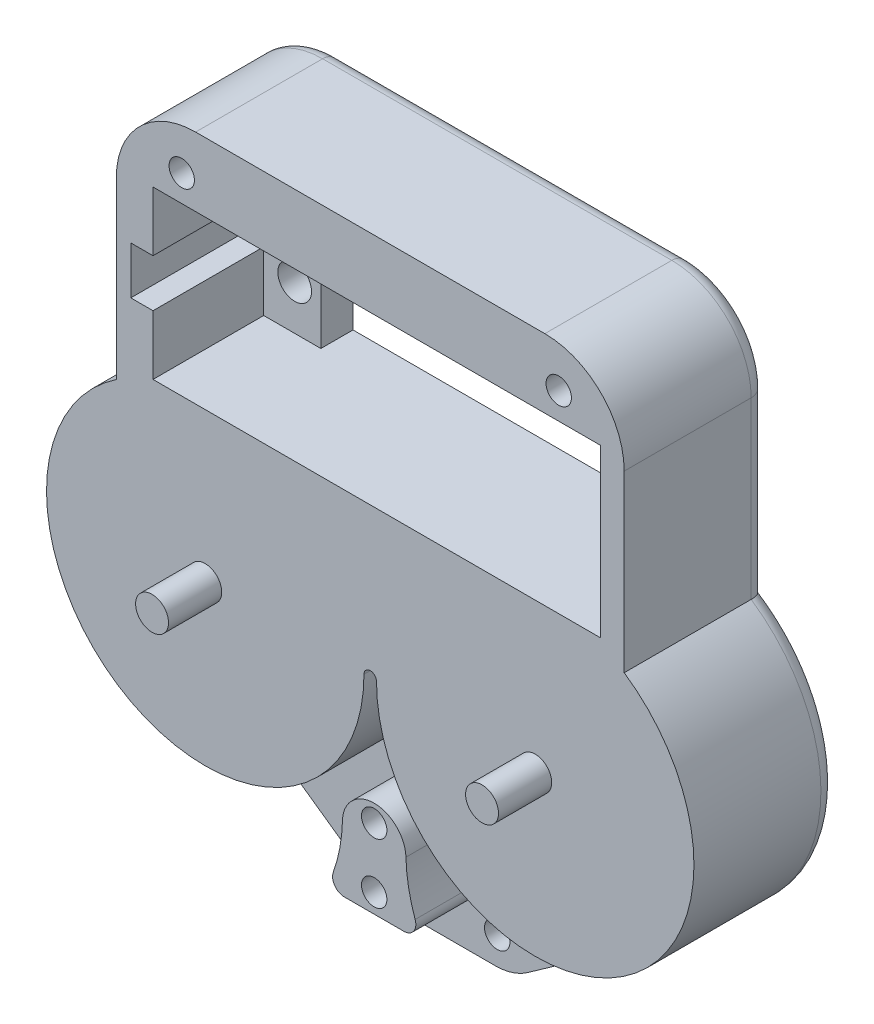
SolidWorks part; units mm, degrees
ref_plane "Alzado" through (0, 0, 0) normal (0, 0, 1) x (1, 0, 0)
ref_plane "Planta" through (0, 0, 0) normal (0, 1, 0) x (1, 0, 0)
ref_plane "Vista lateral" through (0, 0, 0) normal (1, 0, 0) x (0, 0, -1)
sketch "Croquis1" plane through (0, 0, 0) normal (0, 0, 1) x (1, 0, 0)
  line L0 (-9.1775, 40) -> (9.1775, 40)
  line L2 (32.3363, -22.7922) -> (8, -40)
  line L3 (8, -40) -> (-8, -40)
  line L4 (0, 40) -> (0, -40) construction
  line L5 (-32.3363, -22.7922) -> (-8, -40)
  line L7 (24.4498, 13.2001) -> (24.4498, 27.2001)
  line L8 (-24.4498, 13.2001) -> (-24.4498, 27.2001)
  arc A1 (24.4498, 13.2001) -> (32.3363, -22.7922) centre (20.7895, -6.4621) cw
  arc A3 (-24.4498, 13.2001) -> (-32.3363, -22.7922) centre (-20.7895, -6.4621) ccw
  arc A4 (24.4498, 27.2001) -> (9.1775, 40) centre (11.4498, 27.2001) ccw
  arc A5 (-24.4498, 27.2001) -> (-9.1775, 40) centre (-11.4498, 27.2001) cw
  point P7 (0, 0)
  dimension "D4" = 14
  dimension "D5" = 13
  dimension "D2" = 20
  dimension "D1" = 9.1775
  dimension "D3" = 80
  dimension "D6" = 8
extrude "Saliente-Extruir1" add sketch "Croquis1" along normal blind 20 contours A3 L5 L3 L2 A1 L7 A4 L0 A5 L8
sketch "Croquis2" plane through (0, 0, 20) normal (0, 0, 1) x (1, 0, 0)
  line L0 (-20.7895, -6.4621) -> (-0.0045, -6.4621) construction
  line L1 (20.7895, -6.4621) -> (0.0045, -6.4621) construction
  line L2 (0, -40) -> (0, 40) construction
  line L3 (8, -40) -> (-8, -40) construction
  line L4 (-9.1775, 40) -> (9.1775, 40) construction
  arc A0 (0, 2.143) -> (0, -15.0672) centre (-20.7895, -6.4621) ccw
  arc A1 (0, -15.0672) -> (18.9832, 15.9653) centre (20.7895, -6.4621) ccw
  circle A2 centre (-20.7895, -6.4621) radius 20.785 construction
  circle A3 centre (20.7895, -6.4621) radius 20.785 construction
  arc A6 (18.9832, 15.9653) -> (5.6059, 10.1424) centre (8, 22.9201) ccw
  circle A7 centre (8, 22.9201) radius 11.26 construction
  arc A8 (5.6059, 10.1424) -> (0, 2.143) centre (20.7895, -6.4621) ccw
  dimension "D1" = 45
  dimension "D2" = 41.57
  dimension "D3" = 26
  dimension "D4" = 22.52
  dimension "D5" = 8
extrude "Cortar-Extruir1" cut sketch "Croquis2" against normal blind 12 contours A0 A1 A6 A8
sketch "Croquis3" plane through (0, 0, 20) normal (0, 0, 1) x (1, 0, 0)
  line L3 (-23.9199, -28.7432) -> (-8, -40)
  line L4 (-8, -40) -> (8, -40)
  line L5 (8, -40) -> (23.9199, -28.7432)
  line L6 (-23.9199, -28.7432) -> (-8, -40)
  line L7 (-8, -40) -> (8, -40)
  line L8 (8, -40) -> (23.9199, -28.7432)
  arc A2 (0, -15.0672) -> (23.9199, -28.7432) centre (20.7895, -6.4621) ccw
  arc A3 (-23.9199, -28.7432) -> (0, -15.0672) centre (-20.7895, -6.4621) ccw
  arc A4 (0, -15.0672) -> (23.9199, -28.7432) centre (20.7895, -6.4621) ccw
  arc A5 (-23.9199, -28.7432) -> (0, -15.0672) centre (-20.7895, -6.4621) ccw
  dimension "D1" = 0
extrude "Cortar-Extruir2" cut sketch "Croquis3" against normal up to surface (12 mm away) up to face at (1.4203, -0.7032, 8)
sketch "Croquis4" plane through (0, 0, 8) normal (0, 0, 1) x (1, 0, 0)
  circle A0 centre (-20.7895, -6.4621) radius 2.1
  circle A1 centre (20.7895, -6.4621) radius 2.1
  circle A2 centre (8, 22.9201) radius 2.1
  dimension "D1" = 4.2
extrude "Saliente-Extruir2" add sketch "Croquis4" along normal blind 6.7
fillet "Redondeo2" radius 7 2 edges at (8, -40, 4) (-8, -40, 4)
sketch "Croquis5" plane through (0, 0, 8) normal (0, 0, 1) x (1, 0, 0)
  line L0 (0, -40) -> (0, 0) construction
  line L1 (5.7752, -40) -> (-5.7752, -40) construction
  circle A0 centre (6, -36.5) radius 3.5 construction
  circle A1 centre (6, -36.5) radius 1.6
  circle A2 centre (-6, -36.5) radius 1.6
  circle A3 centre (-6, -36.5) radius 3.5 construction
  dimension "D1" = 7
  dimension "D2" = 3.2
  dimension "D3" = 6
extrude "Cortar-Extruir3" cut sketch "Croquis5" against normal through all
sketch "Croquis6" plane through (0, 0, 8) normal (0, 0, 1) x (1, 0, 0)
  line L0 (-6, -32.5) -> (6, -32.5)
  line L2 (0, -40) -> (0, 40) construction
  line L3 (5.7752, -40) -> (-5.7752, -40) construction
  line L4 (0, -32.5) -> (0, -20) construction
  arc A1 (6, -32.5) -> (3.9987, -24.28) centre (23.9921, -23.7658) cw
  arc A2 (3.9987, -24.28) -> (-3.9987, -24.28) centre (0, -24.3828) ccw
  arc A3 (-6, -32.5) -> (-3.9987, -24.28) centre (-23.9921, -23.7658) ccw
  point P3 (0, -32.5)
  dimension "D2" = 20
  dimension "D1" = 7.5
  dimension "D3" = 8.22
  dimension "D4" = 12
  dimension "D6" = 4
extrude "Saliente-Extruir3" add sketch "Croquis6" along normal blind 9.5 contours A1 A2 A3 L0
fillet "Redondeo3" radius 1.5 2 edges at (6, -32.5, 12.75) (-6, -32.5, 12.75)
sketch "Croquis7" plane through (0, 0, 17.5) normal (0, 0, 1) x (1, 0, 0)
  line L0 (0, -32.5) -> (0, -20.3828) construction
  line L1 (-3.7457, -32.5) -> (3.7457, -32.5) construction
  line L2 (0, -20.3828) -> (0, -40) construction
  arc A0 (3.9987, -24.28) -> (-3.9987, -24.28) centre (0, -24.3828) ccw construction
  circle A1 centre (0, -22.5614) radius 1.6
  circle A2 centre (0, -30.1014) radius 1.6
  point P11 (0, -26.4414)
  dimension "D1" = 3.2
  dimension "D2" = 3.88
  dimension "D3" = 3.66
extrude "Cortar-Extruir4" cut sketch "Croquis7" against normal through all
sketch "Croquis8" plane through (0, 0, 20) normal (0, 0, 1) x (1, 0, 0)
  line L3 (24.4498, 15.7382) -> (24.4498, 27.2001)
  line L4 (9.1775, 40) -> (-9.1775, 40)
  line L5 (-24.4498, 27.2001) -> (-24.4498, 15.7382)
  line L6 (24.4498, 15.7382) -> (24.4498, 27.2001)
  line L7 (9.1775, 40) -> (-9.1775, 40)
  line L8 (-24.4498, 27.2001) -> (-24.4498, 15.7382)
  arc A11 (5.6059, 10.1424) -> (0, 2.143) centre (20.7895, -6.4621) ccw
  arc A13 (18.9832, 15.9653) -> (5.6059, 10.1424) centre (8, 22.9201) ccw
  arc A15 (24.4498, 15.7382) -> (18.9832, 15.9653) centre (20.7895, -6.4621) ccw
  arc A17 (24.4498, 27.2001) -> (9.1775, 40) centre (11.4498, 27.2001) ccw
  arc A18 (-9.1775, 40) -> (-24.4498, 27.2001) centre (-11.4498, 27.2001) ccw
  arc A20 (0, 2.143) -> (-24.4498, 15.7382) centre (-20.7895, -6.4621) ccw
  arc A22 (5.6059, 10.1424) -> (0, 2.143) centre (20.7895, -6.4621) ccw
  arc A24 (18.9832, 15.9653) -> (5.6059, 10.1424) centre (8, 22.9201) ccw
  arc A26 (24.4498, 15.7382) -> (18.9832, 15.9653) centre (20.7895, -6.4621) ccw
  arc A28 (24.4498, 27.2001) -> (9.1775, 40) centre (11.4498, 27.2001) ccw
  arc A29 (-9.1775, 40) -> (-24.4498, 27.2001) centre (-11.4498, 27.2001) ccw
  arc A31 (0, 2.143) -> (-24.4498, 15.7382) centre (-20.7895, -6.4621) ccw
  dimension "D1" = 0
extrude "Cortar-Extruir5" cut sketch "Croquis8" against normal up to surface (12 mm away) up to face at (0, -28.5797, 8)
sketch "Croquis9" plane through (0, 0, 14.7) normal (0, 0, 1) x (1, 0, 0)
  circle A0 centre (20.7895, -6.4621) radius 2.1 construction
  circle A1 centre (8, 22.9201) radius 2.1
  circle A2 centre (8, 22.9201) radius 2.1
  circle A3 centre (-20.7895, -6.4621) radius 2.1 construction
  circle A4 centre (20.7895, -6.4621) radius 2.1
  circle A5 centre (-20.7895, -6.4621) radius 2.1
  dimension "D1" = 0
extrude "Cortar-Extruir6" cut sketch "Croquis9" against normal up to surface (6.7 mm away) up to face at (0, -2.5404, 8)
sketch "Croquis10" plane through (0, 0, 8) normal (0, 0, 1) x (1, 0, 0)
  line L0 (24.4498, 13.2001) -> (24.4498, 27.2001) construction
  line L1 (-9.1775, 40) -> (9.1775, 40) construction
  line L2 (-24.4498, 13.2001) -> (-24.4498, 27.2001) construction
  line L3 (24.4498, 13.2001) -> (24.4498, 27.2001)
  line L4 (-9.1775, 40) -> (9.1775, 40)
  line L5 (-24.4498, 13.2001) -> (-24.4498, 27.2001)
  line L6 (24.4498, 13.2001) -> (24.4498, -26.1243) construction
  line L7 (-24.4498, 13.2001) -> (-24.4498, -26.1243) construction
  line L8 (-24.4498, -6.4621) -> (24.4498, -6.4621) construction
  line L9 (20.7895, -6.4621) -> (0.0045, -6.4621) construction
  line L10 (-20.7895, -6.4621) -> (-0.0045, -6.4621) construction
  arc A5 (24.4498, 27.2001) -> (9.1775, 40) centre (11.4498, 27.2001) ccw construction
  arc A6 (-9.1775, 40) -> (-24.4498, 27.2001) centre (-11.4498, 27.2001) ccw construction
  arc A7 (24.4498, 27.2001) -> (9.1775, 40) centre (11.4498, 27.2001) ccw
  arc A8 (-9.1775, 40) -> (-24.4498, 27.2001) centre (-11.4498, 27.2001) ccw
  arc A9 (32.3363, -22.7922) -> (24.4498, 13.2001) centre (20.7895, -6.4621) ccw construction
  arc A10 (-24.4498, 13.2001) -> (-32.3363, -22.7922) centre (-20.7895, -6.4621) ccw construction
  arc A11 (24.4498, -26.1243) -> (24.4498, 13.2001) centre (20.7895, -6.4621) ccw
  arc A12 (-24.4498, 13.2001) -> (-24.4498, -26.1243) centre (-20.7895, -6.4621) ccw
  arc A13 (-24.4498, 13.2001) -> (-0.7895, -6.4621) centre (-20.7895, -6.4621) ccw
  arc A14 (0.7895, -6.4621) -> (24.4498, 13.2001) centre (20.7895, -6.4621) ccw
  arc A15 (-0.7895, -6.4621) -> (0.7895, -6.4621) centre (0, -6.4621) cw
sketch "Croquis11" plane through (0, 0, 8) normal (0, 0, 1) x (1, 0, 0)
  line L0 (24.4498, 13.2001) -> (24.4498, 27.2001) construction
  line L1 (-9.1775, 40) -> (9.1775, 40) construction
  line L2 (-24.4498, 13.2001) -> (-24.4498, 27.2001) construction
  line L3 (24.4498, 13.2001) -> (24.4498, 27.2001)
  line L4 (-9.1775, 40) -> (9.1775, 40)
  line L5 (-24.4498, 13.2001) -> (-24.4498, 27.2001)
  arc A0 (24.4498, 27.2001) -> (9.1775, 40) centre (11.4498, 27.2001) ccw construction
  arc A1 (-9.1775, 40) -> (-24.4498, 27.2001) centre (-11.4498, 27.2001) ccw construction
  arc A2 (24.4498, 27.2001) -> (9.1775, 40) centre (11.4498, 27.2001) ccw
  arc A3 (-9.1775, 40) -> (-24.4498, 27.2001) centre (-11.4498, 27.2001) ccw
  arc A4 (32.3363, -22.7922) -> (24.4498, 13.2001) centre (20.7895, -6.4621) ccw construction
  arc A5 (-24.4498, 13.2001) -> (-32.3363, -22.7922) centre (-20.7895, -6.4621) ccw construction
  arc A6 (24.4498, -26.1243) -> (24.4498, 13.2001) centre (20.7895, -6.4621) ccw
  arc A7 (-24.4498, 13.2001) -> (-24.4498, -26.1243) centre (-20.7895, -6.4621) ccw
  arc A8 (-24.4498, -26.1243) -> (-0.7895, -6.4621) centre (-20.7895, -6.4621) ccw
  arc A9 (24.4498, -26.1243) -> (0.7895, -6.4621) centre (20.7895, -6.4621) cw
  arc A10 (-0.7895, -6.4621) -> (0.7895, -6.4621) centre (0, -6.4621) cw
extrude "Saliente-Extruir4" add sketch "Croquis11" along normal blind 10
sketch "Croquis12" plane through (0, 0, 18) normal (0, 0, 1) x (1, 0, 0)
  circle A0 centre (-20.7895, -6.4621) radius 2.075
  circle A1 centre (20.7895, -6.4621) radius 2.075
  dimension "D1" = 4.15
extrude "Saliente-Extruir5" add sketch "Croquis12" along normal blind 6.7
sketch "Croquis14" plane through (0, 0, 18) normal (0, 0, 1) x (1, 0, 0)
  line L1 (-32, 32.1007) -> (-32, 10.1007)
  line L2 (-24.4498, 27.2001) -> (-24.4498, 13.2001) construction
  line L3 (-24.4498, 27.2001) -> (-24.4498, 13.2001)
  line L4 (-22, 42.1007) -> (22, 42.1007)
  line L5 (32, 32.1007) -> (32, 10.1007)
  line L6 (24.4498, 13.2001) -> (24.4498, 27.2001) construction
  line L7 (9.1775, 40) -> (-9.1775, 40) construction
  line L8 (24.4498, 13.2001) -> (24.4498, 27.2001)
  line L9 (9.1775, 40) -> (-9.1775, 40)
  arc A0 (-24.4498, 13.2001) -> (-0.7895, -6.4621) centre (-20.7895, -6.4621) ccw construction
  arc A1 (-9.1775, 40) -> (-24.4498, 27.2001) centre (-11.4498, 27.2001) ccw construction
  arc A2 (-9.1775, 40) -> (-24.4498, 27.2001) centre (-11.4498, 27.2001) ccw
  arc A3 (-24.4498, 13.2001) -> (-32, 10.1007) centre (-20.7895, -6.4621) ccw
  arc A4 (0.7895, -6.4621) -> (24.4498, 13.2001) centre (20.7895, -6.4621) ccw construction
  arc A5 (24.4498, 27.2001) -> (9.1775, 40) centre (11.4498, 27.2001) ccw construction
  arc A6 (32, 10.1007) -> (24.4498, 13.2001) centre (20.7895, -6.4621) ccw
  arc A7 (24.4498, 27.2001) -> (9.1775, 40) centre (11.4498, 27.2001) ccw
  arc A8 (22, 42.1007) -> (32, 32.1007) centre (22, 32.1007) cw
  arc A9 (-22, 42.1007) -> (-32, 32.1007) centre (-22, 32.1007) ccw
  point P5 (0, 42.1007)
  point P23 (-32, 42.1007)
  dimension "D3" = 10
  dimension "D1" = 32
  dimension "D2" = 64
extrude "Saliente-Extruir6" add sketch "Croquis14" against normal up to surface (18 mm away) up to face at (1.6, -22.5614, 0)
fillet "Redondeo1" radius 2 12 edges at (-40.7884, -6.2576, 0) (-21.0764, -30.7538, 0) (0, -40, 0) (21.0764, -30.7538, 0) (40.7884, -6.2576, 0) (29.0711, 39.1717, 0) (0, 42.1007, 0) (-29.0711, 39.1717, 0) (-32, 21.1007, 0) (-7.8955, -39.6712, 0) (7.8955, -39.6712, 0) (32, 21.1007, 0)
sketch "Croquis13" plane through (0, 0, 18) normal (0, 0, 1) x (1, 0, 0)
  line L0 (0.83, 33.4201) -> (0.83, 12.4201) construction
  line L5 (-27.37, 33.4201) -> (29.03, 33.4201)
  line L6 (-27.37, 33.4201) -> (-27.37, 12.4201)
  line L7 (-27.37, 12.4201) -> (29.03, 12.4201)
  line L8 (29.03, 33.4201) -> (29.03, 12.4201)
  point P4 (29.03, 22.9201)
  dimension "D1" = 21.03
  dimension "D2" = 56.4
  dimension "D3" = 21
extrude "Cortar-Extruir7" cut sketch "Croquis13" against normal blind 13.95
sketch "Croquis15" plane through (0, 0, 4.05) normal (0, 0, 1) x (1, 0, 0)
  line L5 (29.03, 33.4201) -> (-27.37, 33.4201) construction
  line L6 (-20.17, 33.4201) -> (21.83, 33.4201)
  line L13 (-20.17, 33.4201) -> (-20.17, 12.4201)
  line L14 (-20.17, 12.4201) -> (21.83, 12.4201)
  line L15 (21.83, 33.4201) -> (21.83, 12.4201)
  line L16 (-27.37, 12.4201) -> (29.03, 12.4201) construction
  line L17 (0.83, 33.4201) -> (0.83, 12.4201) construction
  point P5 (0.83, 33.4201)
  dimension "D1" = 42
extrude "Cortar-Extruir8" cut sketch "Croquis15" against normal through all
sketch "Croquis16" [suppressed] plane through (0, 0, 4.05) normal (0, 0, 1) x (1, 0, 0)
  circle A0 centre (1.5743, 28.719) radius 2.125
  circle A1 centre (1.5743, 18.969) radius 2.125
  circle A2 centre (50.1743, 28.719) radius 2.125
  circle A3 centre (50.1743, 18.969) radius 2.125
sketch "Croquis18" plane through (0, 0, 0) normal (0, 0, -1) x (-1, 0, 0)
  circle A0 centre (0, -22.5614) radius 3.66
  circle A2 centre (6, -36.5) radius 3.66
  circle A3 centre (-6, -36.5) radius 3.66
  circle A4 centre (0, -30.1014) radius 3.66
  dimension "D1" = 7.32
extrude "Cortar-Extruir11" cut sketch "Croquis18" against normal blind 2.67
sketch "Croquis17" plane through (0, 0, 0) normal (0, 0, -1) x (-1, 0, 0)
  line L1 (-43.4093, 11.1522) -> (43.8711, 11.1522)
  line L2 (-43.4093, 11.1522) -> (-43.4093, -41.3776)
  line L3 (-43.4093, -41.3776) -> (43.8711, -41.3776)
  line L4 (43.8711, 11.1522) -> (43.8711, -41.3776)
sketch "Croquis19" plane through (0, 0, 0) normal (0, 0, -1) x (-1, 0, 0)
  line L6 (20.17, 25.9201) -> (30.17, 25.9201)
  line L7 (20.17, 25.9201) -> (20.17, 19.9201)
  line L8 (20.17, 19.9201) -> (30.17, 19.9201)
  line L9 (30.17, 25.9201) -> (30.17, 19.9201)
  line L10 (20.17, 33.4201) -> (20.17, 12.4201) construction
  point P4 (20.17, 22.9201)
  point P5 (20.17, 22.9201)
  dimension "D1" = 10
  dimension "D2" = 6
extrude "Cortar-Extruir12" cut sketch "Croquis19" against normal through all
sketch "Croquis20" plane through (0, 0, 4.05) normal (0, 0, 1) x (1, 0, 0)
  circle A0 centre (25.13, 27.7951) radius 2.125
  circle A1 centre (25.13, 18.0451) radius 2.125
  circle A2 centre (-23.47, 27.7951) radius 2.125
  circle A3 centre (-23.47, 18.0451) radius 2.125
extrude "Cortar-Extruir13" cut sketch "Croquis20" against normal through all
sketch "Croquis21" plane through (0, 0, 0) normal (0, 0, -1) x (-1, 0, 0)
  line L0 (0, 33.4201) -> (0, 40.1007) construction
  line L1 (20.17, 33.4201) -> (-21.83, 33.4201) construction
  line L2 (22, 40.1007) -> (-22, 40.1007) construction
  circle A0 centre (23.75, 36.7604) radius 1.6
  circle A1 centre (23.75, 36.7604) radius 3.66 construction
  circle A2 centre (-23.75, 36.7604) radius 1.6
  point P9 (0, 36.7604)
  dimension "D1" = 3.2
  dimension "D2" = 7.32
  dimension "D3" = 23.75
extrude "Cortar-Extruir14" cut sketch "Croquis21" against normal through all
sketch "Croquis22" plane through (0, 0, 0) normal (0, 0, -1) x (-1, 0, 0)
  circle A0 centre (-23.75, 36.7604) radius 3.66
  circle A1 centre (23.75, 36.7604) radius 3.66
  dimension "D1" = 7.32
extrude "Cortar-Extruir15" cut sketch "Croquis22" against normal blind 2.67
sketch "Croquis23" plane through (0, 0, 0) normal (0, 0, -1) x (-1, 0, 0)
  line L1 (-49.443, 10.2444) -> (45.1106, 10.2444)
  line L2 (-49.443, 10.2444) -> (-49.443, -41.078)
  line L3 (-49.443, -41.078) -> (45.1106, -41.078)
  line L4 (45.1106, 10.2444) -> (45.1106, -41.078)
  point P4 (-48.5183, 10.0132)
  point P5 (-49.443, 10.2444)
